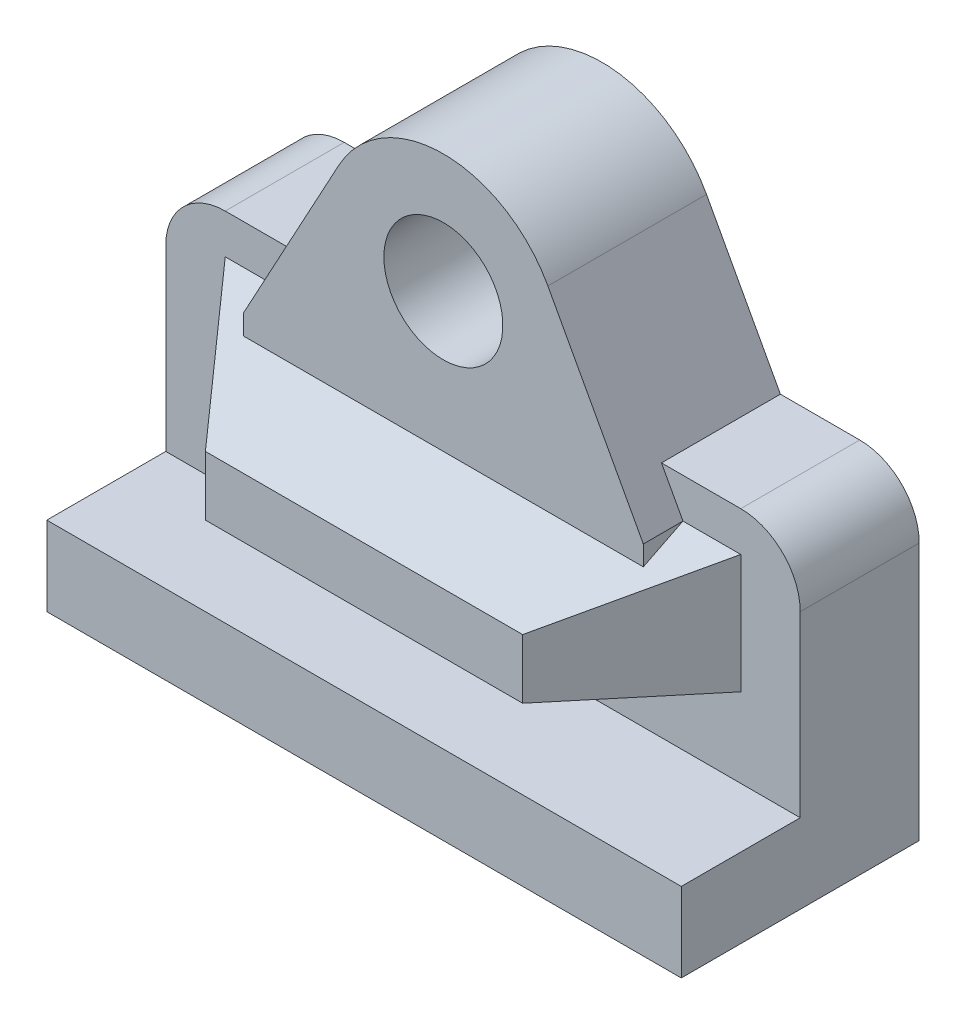
SolidWorks part; units mm, degrees
ref_plane "Front Plane" through (0, 0, 0) normal (0, 0, 1) x (1, 0, 0)
ref_plane "Top Plane" through (0, 0, 0) normal (0, 1, 0) x (1, 0, 0)
ref_plane "Right Plane" through (0, 0, 0) normal (1, 0, 0) x (0, 0, -1)
sketch "Sketch1" plane through (0, 0, 0) normal (0, 0, 1) x (1, 0, 0)
  line L0 (0, 0) -> (101.6, 0)
  line L1 (101.6, 0) -> (101.6, 41.275)
  line L2 (92.075, 50.8) -> (79.375, 50.8)
  line L3 (50.8, 0) -> (50.8, 25.4) construction
  line L4 (101.6, 12.7) -> (0, 12.7)
  line L5 (0, 12.7) -> (0, 0)
  line L6 (50.8, 25.4) -> (101.6, 25.4) construction
  line L7 (67.5406, 72.5914) -> (79.375, 50.8)
  line L8 (50.8, 63.5) -> (50.8, 82.55) construction
  line L9 (34.0594, 72.5914) -> (22.225, 50.8)
  line L10 (9.525, 50.8) -> (22.225, 50.8)
  line L11 (0, 0) -> (0, 41.275)
  line L12 (0, 44.45) -> (101.6, 44.45) construction
  line L13 (6.35, 44.45) -> (95.25, 44.45)
  line L14 (95.25, 44.45) -> (95.25, 25.4)
  line L15 (95.25, 25.4) -> (6.35, 25.4)
  line L16 (6.35, 44.45) -> (6.35, 25.4)
  line L17 (50.8, 44.45) -> (50.8, 63.5) construction
  circle A0 centre (50.8, 63.5) radius 9.525
  arc A1 (67.5406, 72.5914) -> (34.0594, 72.5914) centre (50.8, 63.5) ccw
  arc A2 (0, 41.275) -> (9.525, 50.8) centre (9.525, 41.275) cw
  arc A3 (101.6, 41.275) -> (92.075, 50.8) centre (92.075, 41.275) ccw
  point P24 (50.8, 44.45)
  point P26 (0, 50.8)
  point P29 (101.6, 50.8)
  dimension "D6" = 19.05
  dimension "D7" = 38.1
  dimension "D11" = 9.525
  dimension "D1" = 101.6
  dimension "D2" = 50.8
  dimension "D3" = 12.7
  dimension "D4" = 12.7
  dimension "D5" = 38.1
  dimension "D8" = 28.575
  dimension "D9" = 19.05
  dimension "D10" = 44.45
extrude "Boss-Extrude1" add sketch "Sketch1" along normal blind 19.05 contours L1 A3 L2 L7 A1 L9 L10 A2 L11 L4 L16 L13 L14 L15 A0 | L13 L16 L15 L14 region at (1.2329, 26.9875, 0) region at (50.8, 34.925, 0)
extrude "Boss-Extrude2" add sketch "Sketch1<3>" along normal blind 38.1 contours L4 L5 L0 L1 region at (50.8, 6.35, 0)
sketch "Sketch1<3>" plane through (0, 0, 0) normal (0, 0, 1) x (1, 0, 0) same geometry as "Sketch1"
sketch "Sketch2" plane through (0, 0, 38.1) normal (0, 0, 1) x (1, 0, 0)
  line L0 (50.8, 12.7) -> (50.8, 53.975) construction
  line L1 (101.6, 12.7) -> (0, 12.7) construction
  line L2 (25.4, 25.4) -> (76.2, 25.4)
  line L3 (76.2, 25.4) -> (76.2, 34.925)
  line L4 (76.2, 34.925) -> (25.4, 34.925)
  line L5 (25.4, 25.4) -> (25.4, 34.925)
  circle A0 centre (50.8, 63.5) radius 9.525 construction
  point P12 (50.8, 34.925)
  point P13 (50.8, 25.4)
  dimension "D1" = 12.7
  dimension "D2" = 25.4
  dimension "D3" = 9.525
sketch "Sketch5" plane through (0, 0, 19.05) normal (0, 0, 1) x (1, 0, 0)
  line L0 (101.6, 12.7) -> (0, 12.7) construction
  line L1 (9.525, 25.4) -> (92.075, 25.4)
  line L2 (9.525, 25.4) -> (9.525, 44.45)
  line L3 (9.525, 44.45) -> (92.075, 44.45)
  line L4 (92.075, 25.4) -> (92.075, 44.45)
  line L5 (50.8, 12.7) -> (50.8, 53.975) construction
  point P6 (50.8, 25.4)
  dimension "D1" = 12.7
  dimension "D2" = 82.55
  dimension "D3" = 19.05
loft "Loft1" add profiles "Sketch5", "Sketch2"
sketch "Sketch6" plane through (0, 0, 19.05) normal (0, 0, 1) x (1, 0, 0)
  line L0 (34.0594, 72.5914) -> (18.7765, 44.45)
  line L1 (92.075, 44.45) -> (9.525, 44.45) construction
  line L2 (67.5406, 72.5914) -> (82.8235, 44.45)
  line L3 (82.8235, 44.45) -> (18.7765, 44.45)
  circle A0 centre (50.8, 63.5) radius 9.525
  arc A1 (67.5406, 72.5914) -> (34.0594, 72.5914) centre (50.8, 63.5) ccw
  dimension "D1" = 19.05
extrude "Boss-Extrude6" add sketch "Sketch6" along normal blind 6.35
sketch "Sketch7" plane through (0, 44.45, 0) normal (0, -1, 0) x (1, 0, 0)
  line L1 (18.7765, 19.05) -> (82.8235, 19.05)
  line L2 (18.7765, 19.05) -> (18.7765, 25.4)
  line L3 (18.7765, 25.4) -> (82.8235, 25.4)
  line L4 (82.8235, 19.05) -> (82.8235, 25.4)
extrude "Boss-Extrude7" add sketch "Sketch7" along normal up to surface up to face at (56.5752, 42.8625, 22.225)
